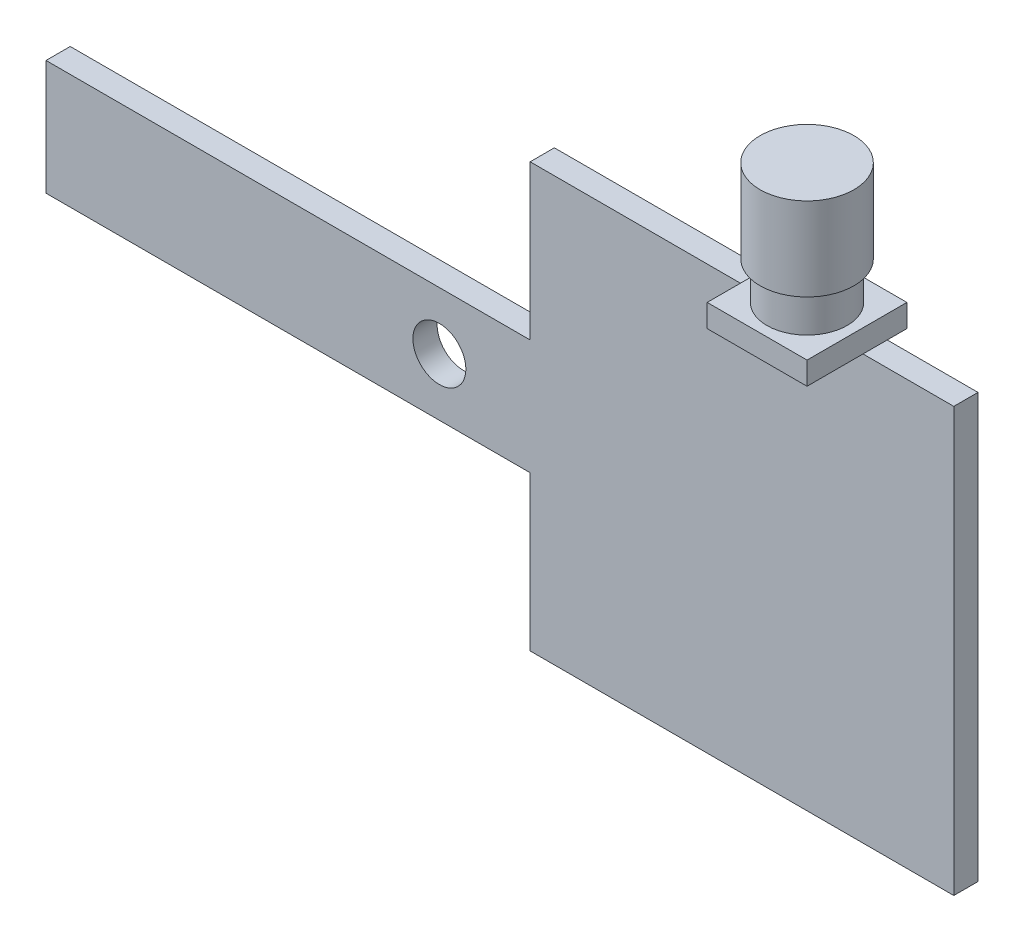
SolidWorks part; units mm, degrees
ref_plane "Front Plane" through (0, 0, 0) normal (0, 0, 1) x (1, 0, 0)
ref_plane "Top Plane" through (0, 0, 0) normal (0, 1, 0) x (1, 0, 0)
ref_plane "Right Plane" through (0, 0, 0) normal (1, 0, 0) x (0, 0, -1)
sketch "Sketch1" plane through (0, 0, 0) normal (0, 0, 1) x (1, 0, 0)
  line L0 (0, 0) -> (-6, 0) construction
  line L1 (0, 14) -> (28, 14)
  line L2 (0, 14) -> (0, -14)
  line L3 (0, -14) -> (28, -14)
  line L4 (28, 14) -> (28, -14)
  line L5 (-32, 3.8) -> (0, 3.8)
  line L6 (-32, 3.8) -> (-32, -3.8)
  line L7 (-32, -3.8) -> (0, -3.8)
  line L8 (0, 3.8) -> (0, -3.8)
  circle A0 centre (-6, 0) radius 1.75
  point P4 (0, 0)
  point P10 (0, 0)
  dimension "D5" = 3.5
  dimension "D1" = 28
  dimension "D2" = 28
  dimension "D3" = 7.6
  dimension "D4" = 60
  dimension "D6" = 26
  dimension "D7" = 34
extrude "Boss-Extrude1" add sketch "Sketch1" along normal blind 1.6 contours L6 L7 L8 A0 L2 L5 | L4 L1 L2 L8 L3 region at (14, 0, 0) region at (-16.4119, 0, 0)
sketch "Sketch2" plane through (0, 14, 0) normal (0, 1, 0) x (1, 0, 0)
  line L0 (28, -1.6) -> (28, 0) construction
  line L1 (15.4, 1.3) -> (22, 1.3)
  line L2 (15.4, 1.3) -> (15.4, -5.3)
  line L3 (15.4, -5.3) -> (22, -5.3)
  line L4 (22, 1.3) -> (22, -5.3)
  line L5 (0, -1.6) -> (0, 0) construction
  line L6 (0, -1.6) -> (28, -1.6) construction
  line L8 (0, 0) -> (28, 0) construction
  point P6 (28, -0.8)
  dimension "D1" = 6.6
  dimension "D2" = 6.6
  dimension "D3" = 6
  dimension "D4" = 15.4
  dimension "D5" = 2.9
  dimension "D6" = 5.3
extrude "Boss-Extrude2" add sketch "Sketch2" along normal blind 1.5 separate body
sketch "Sketch3" plane through (0, 15.5, 0) normal (0, 1, 0) x (1, 0, 0)
  line L0 (15.4, 1.3) -> (22, -5.3) construction
  circle A0 centre (18.7, -2) radius 2.65
  dimension "D1" = 5.3
extrude "Boss-Extrude3" add sketch "Sketch3" along normal blind 2.5
sketch "Sketch4" plane through (0, 18, 0) normal (0, 1, 0) x (1, 0, 0)
  circle A0 centre (18.7, -2) radius 3.1
  dimension "D1" = 6.2
extrude "Boss-Extrude4" add sketch "Sketch4" along normal blind 5.5
